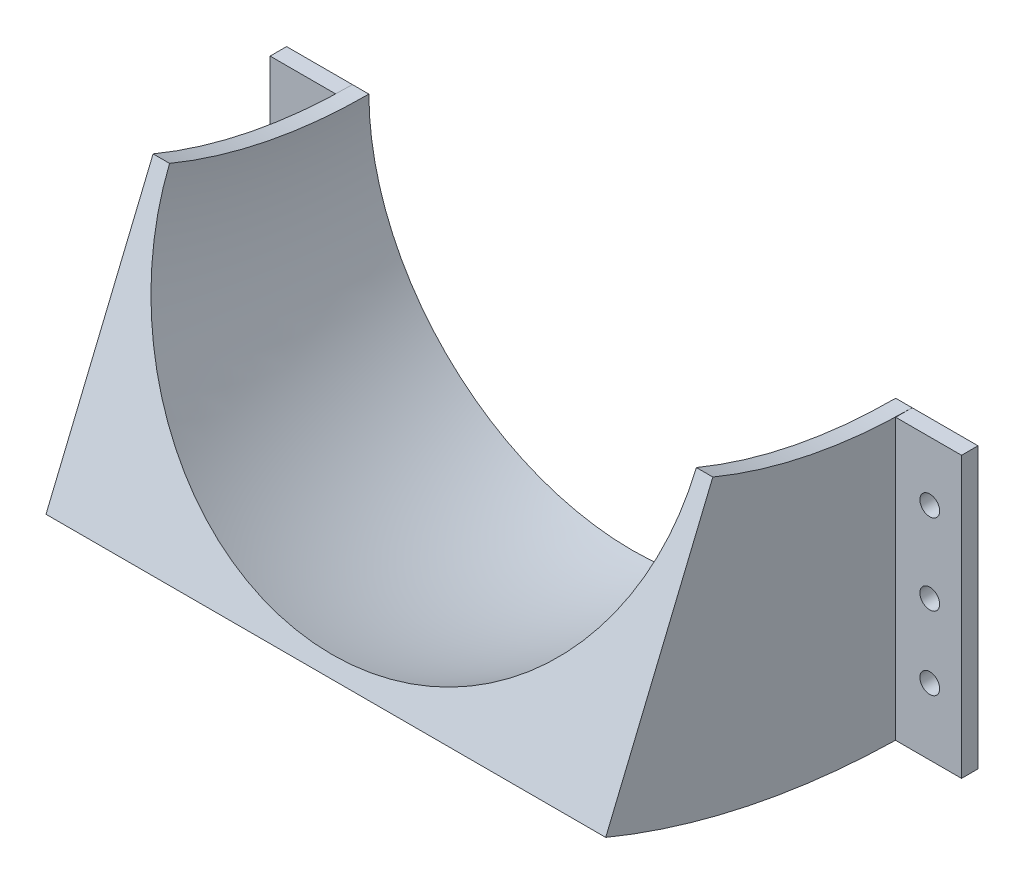
SolidWorks part; units mm, degrees
ref_plane "Front Plane" through (0, 0, 0) normal (0, 0, 1) x (1, 0, 0)
ref_plane "Top Plane" through (0, 0, 0) normal (0, 1, 0) x (1, 0, 0)
ref_plane "Right Plane" through (0, 0, 0) normal (1, 0, 0) x (0, 0, -1)
sketch "Sketch9" plane through (0, 0, 0) normal (0, 0, 1) x (1, 0, 0)
  line L0 (50.8, -100.457) -> (53.975, -100.457)
  line L1 (-50.8, -100.457) -> (-53.975, -100.457)
  line L2 (53.975, -100.457) -> (53.975, -154.432)
  line L3 (-53.975, -100.457) -> (-53.975, -154.432)
  line L4 (-53.975, -154.432) -> (53.975, -154.432)
  line L5 (-53.975, -154.432) -> (53.975, -154.432) construction
  arc A0 (50.8, -100.457) -> (-50.8, -100.457) centre (0, -100.457) cw
  dimension "D1" = 50.8
  dimension "D2" = 3.175
  dimension "D3" = 53.975
  dimension "D4" = 0
ref_axis "Axis2" through (-38.0489, 0, 0) along (1, 0, 0)
revolve "Revolve8" add sketch "Sketch9" angle 22.5 about axis through (-38.0489, 0, 0) along (1, 0, 0) reverse direction yes
sketch "Sketch10" plane through (53.975, 0, 0) normal (1, 0, 0) x (0, 0, -1)
  line L0 (0, -100.457) -> (0, -154.432)
  line L1 (0, -100.457) -> (-3.175, -100.457)
  line L2 (0, -154.432) -> (-3.175, -154.432)
  line L3 (-3.175, -100.457) -> (-3.175, -154.432)
  dimension "D1" = 3.175
sketch "Sketch11" plane through (-53.975, 0, 0) normal (-1, 0, 0) x (0, 0, 1)
  line L0 (0, -154.432) -> (0, -100.457)
  line L1 (0, -154.432) -> (3.175, -154.432)
  line L2 (0, -100.457) -> (3.175, -100.457)
  line L3 (3.175, -154.432) -> (3.175, -100.457)
  dimension "D1" = 3.175
extrude "Boss-Extrude3" add sketch "Sketch11" along normal blind 12.7
extrude "Boss-Extrude4" add sketch "Sketch10" along normal blind 12.7
sketch "Sketch12" plane through (0, 0, 3.175) normal (0, 0, 1) x (1, 0, 0)
  circle A1 centre (60.5502, -111.886) radius 1.905
  circle A2 centre (60.5502, -111.886) radius 1.905
  circle A3 centre (60.5502, -141.5668) radius 1.905
  circle A4 centre (60.5502, -141.5668) radius 1.905
  circle A5 centre (60.5502, -127.4445) radius 1.905
  circle A6 centre (60.5502, -127.4445) radius 1.905
  dimension "D1" = 0
  dimension "D2" = 0
  dimension "D3" = 0
extrude "Cut-Extrude4" cut sketch "Sketch12" against normal blind 3.175
sketch "Sketch13" plane through (0, 0, 3.175) normal (0, 0, 1) x (1, 0, 0)
  circle A1 centre (-60.754, -141.5219) radius 1.905
  circle A2 centre (-60.754, -141.5219) radius 1.905
  circle A3 centre (-60.754, -112.4795) radius 1.905
  circle A4 centre (-60.754, -112.4795) radius 1.905
  circle A5 centre (-60.754, -127.4445) radius 1.905
  circle A6 centre (-60.754, -127.4445) radius 1.905
  dimension "D1" = 0
  dimension "D2" = 0
  dimension "D3" = 0
extrude "Cut-Extrude5" cut sketch "Sketch13" against normal blind 3.175
ref_plane "Back Plane" through (0, -100.8876, 100.8876) normal (0, -0.7071, 0.7071) x (1, 0, 0)
